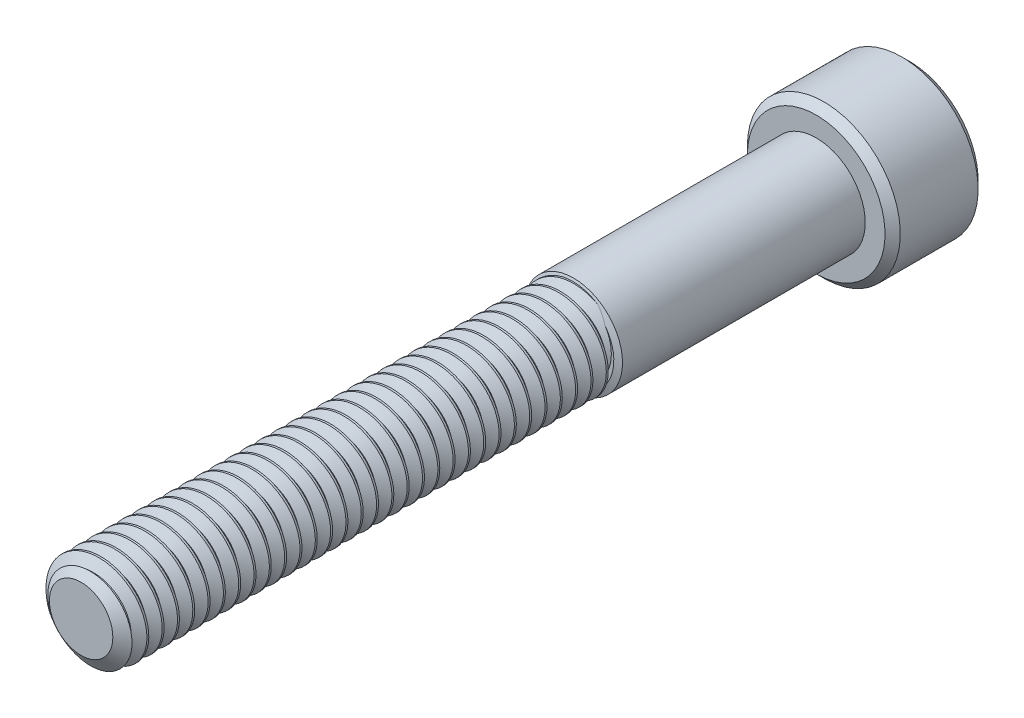
SolidWorks part; units mm, degrees
ref_plane "Front Plane" through (0, 0, 0) normal (0, 0, 1) x (1, 0, 0)
ref_plane "Top Plane" through (0, 0, 0) normal (0, 1, 0) x (1, 0, 0)
ref_plane "Right Plane" through (0, 0, 0) normal (1, 0, 0) x (0, 0, -1)
sketch "Sketch1" plane through (0, 0, 0) normal (0, 0, 1) x (1, 0, 0)
  circle A0 centre (0, 0) radius 2.413
  dimension "OD" = 4.826
extrude "Extrude1" add sketch "Sketch1" against normal blind 38.1
sketch "Sketch2" plane through (0, 0, 0) normal (0, 0, 1) x (1, 0, 0)
  circle A0 centre (0, 0) radius 2.413 construction
  circle A1 centre (0, 0) radius 2.413
curve "Helix/Spiral1" pitch 0.7937 height 38.8938 turns 49 parameters "pitch"=0.7937
sketch "Sketch3" plane through (0, 0, 0) normal (1, 0, 0) x (0, 0, -1)
  line L0 (-0.6945, 2.413) -> (-0.3969, 1.8974)
  line L1 (-0.3969, 1.8974) -> (-0.2977, 1.8974)
  line L2 (-0.2977, 1.8974) -> (0, 2.413)
  line L3 (-0.6945, 2.413) -> (0, 2.413)
  line L4 (-0.3473, 2.413) -> (-0.3473, 1.8974) construction
  line L5 (-0.5457, 2.1552) -> (-0.1488, 2.1552) construction
  line L6 (0, 2.413) -> (0, -2.413) construction
  dimension "D1" = 0.0992
  dimension "D2" = 0.3969
  dimension "D3" = 60
sweep "Cut-Sweep1" cut profiles "Sketch3" path "Helix/Spiral1"
sketch "Sketch4" plane through (0, 0, 0) normal (1, 0, 0) x (0, 0, -1)
  line L0 (0.5388, 2.413) -> (0, 1.6434)
  line L1 (0, 1.6434) -> (0, 2.413)
  line L2 (0.5388, 2.413) -> (0, 2.413)
  line L3 (-0.6945, 2.413) -> (0, 2.413) construction
  line L4 (0, 0) -> (7.0209, 0) construction
  dimension "D1" = 55
  dimension "D2" = 0.254
revolve "Cut-Revolve1" cut sketch "Sketch4" angle 360 about L4
sketch "Sketch5" plane through (0, 0, 0) normal (1, 0, 0) x (0, 0, -1)
  line L0 (38.1, -1.9083) -> (38.1, 1.7217) construction
  line L1 (38.1, 2.54) -> (25.5202, 2.54)
  line L2 (38.1, 2.54) -> (38.1, 0)
  line L3 (38.1, 0) -> (25.4, 0)
  line L4 (25.4, 2.2098) -> (25.4, 0)
  line L5 (25.5202, 2.54) -> (25.4, 2.2098)
  line L6 (0, 0) -> (9.9695, 0) construction
  point P3 (25.4, 2.54)
  point P10 (25.4, 2.54)
  dimension "D1" = 0.3302
  dimension "Thread min" = 25.4
  dimension "D2" = 0.127
  dimension "D3" = 20
revolve "partially thread" add sketch "Sketch5" angle 360 about L6
sketch "Sketch6" plane through (0, 0, -38.1) normal (0, 0, -1) x (-1, 0, 0)
  circle A0 centre (0, 0) radius 3.9624
  dimension "head dia" = 7.9248
extrude "Extrude2" add sketch "Sketch6" along normal blind 4.826
sketch "Sketch7" plane through (0, 0, -42.926) normal (0, 0, -1) x (-1, 0, 0)
  line L1 (0, 2.2914) -> (-1.9844, 1.1457)
  line L2 (-1.9844, 1.1457) -> (-1.9844, -1.1457)
  line L3 (-1.9844, -1.1457) -> (0, -2.2914)
  line L4 (0, -2.2914) -> (1.9844, -1.1457)
  line L5 (1.9844, -1.1457) -> (1.9844, 1.1457)
  line L6 (1.9844, 1.1457) -> (0, 2.2914)
  circle A0 centre (0, 0) radius 1.9844 construction
  dimension "hex dia" = 3.9688
extrude "Cut-Extrude1" cut sketch "Sketch7" against normal blind 2.9766
sketch "Sketch8" plane through (0, 0, -42.926) normal (0, 0, -1) x (-1, 0, 0)
  circle A0 centre (0, 0) radius 2.2914
extrude "Cut-Extrude2" cut sketch "Sketch8" against normal through all draft 45
chamfer "Chamfer1" distance 0.3962 angle 45 2 edges at (-3.9624, 0, -42.926) (-3.9624, 0, -38.1)
sketch "Sketch9" plane through (0, 0, 0) normal (1, 0, 0) x (0, 0, -1)
  line L0 (0, 2.413) -> (0, -2.413) construction
  line L1 (4.3656, 2.413) -> (4.3656, -2.413) construction
  dimension "D1" = 4.3656
equation "\"D3@Helix/Spiral1\" = \"screw length@Extrude1\"+\"pitch@Helix/Spiral1\""
equation "\"D1@Sketch3\" = \"pitch@Helix/Spiral1\"*.125"
equation "\"D2@Sketch3\" = \"pitch@Helix/Spiral1\"*.5"
equation "\"D1@Cut-Extrude1\" = \"hex dia@Sketch7\"*.75"
equation "\"D1@Chamfer1\" = \"head dia@Sketch6\"*.05"
equation "\"D1@Sketch9\" = \"pitch@Helix/Spiral1\"*5.5"
